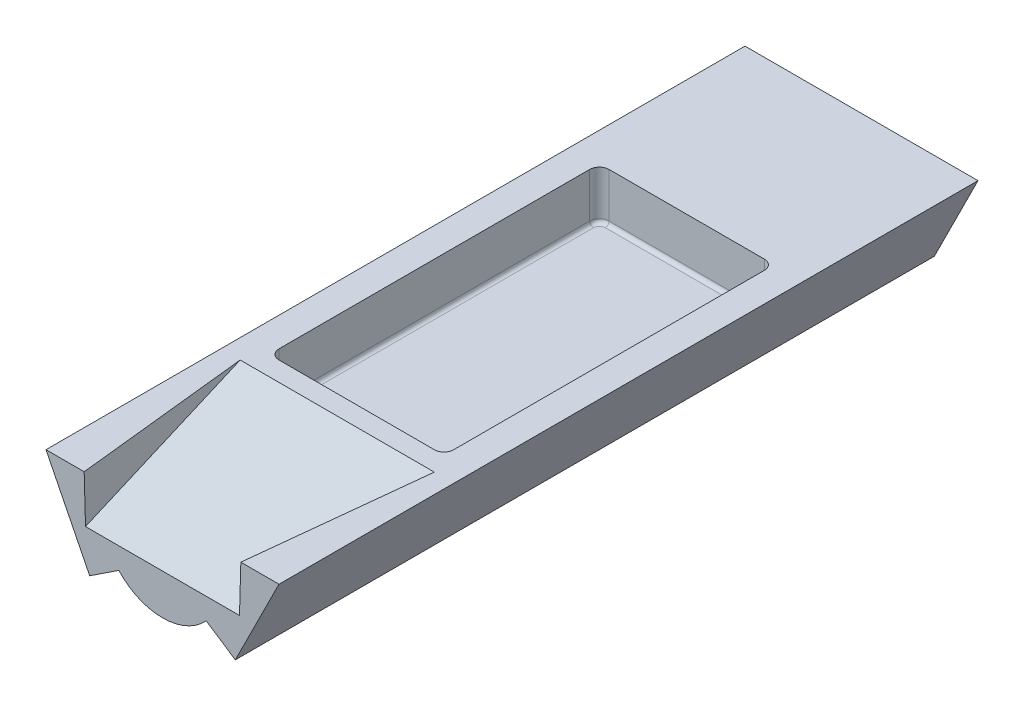
SolidWorks part; units mm, degrees
ref_plane "Front Plane" through (0, 0, 0) normal (0, 0, 1) x (1, 0, 0)
ref_plane "Top Plane" through (0, 0, 0) normal (0, 1, 0) x (1, 0, 0)
ref_plane "Right Plane" through (0, 0, 0) normal (1, 0, 0) x (0, 0, -1)
sketch "Sketch1" plane through (0, 0, 0) normal (0, 0, 1) x (1, 0, 0)
  line L6 (-304.8, 228.6) -> (304.8, 228.6)
  line L9 (0, 0) -> (0, 228.6) construction
  line L15 (-304.8, 228.6) -> (-190.5, 0)
  line L16 (-190.5, 0) -> (-114.3, 50.4)
  line L18 (190.5, 0) -> (304.8, 228.6)
  line L19 (190.5, 0) -> (114.3, 50.4)
  arc A0 (-114.3, 50.4) -> (114.3, 50.4) centre (0, 154.808) ccw
  dimension "D1" = 609.6
  dimension "D2" = 228.6
  dimension "D3" = 228.6
  dimension "D4" = 114.3
  dimension "D5" = 114.3
  dimension "D6" = 76.2
  dimension "D7" = 76.2
extrude "Boss-Extrude2" add sketch "Sketch1" against normal blind 1828.8
sketch "Sketch2" plane through (0, 228.6, 0) normal (0, 1, 0) x (1, 0, 0)
  line L1 (-203.2, 0) -> (203.2, 0)
  line L3 (-254, 457.2) -> (254, 457.2)
  line L6 (-254, 457.2) -> (-203.2, 0)
  line L7 (254, 457.2) -> (203.2, 0)
  line L8 (304.8, 0) -> (-304.8, 0) construction
  dimension "D1" = 508
  dimension "D2" = 457.2
  dimension "D3" = 50.8
  dimension "D4" = 50.8
ref_plane "Plane1" through (0, 98.9867, 26.5234) normal (0, 0.9659, 0.2588) x (1, 0, 0)
sketch "Sketch7" plane through (0, 98.9867, 26.5234) normal (0, 0.9659, 0.2588) x (1, 0, 0)
  line L1 (-254, 500.7873) -> (254, 500.7873)
  line L2 (-254, 500.7873) -> (-196.5534, -16.2318)
  line L3 (254, 500.7873) -> (196.5534, -16.2318)
  line L6 (-196.5534, -16.2318) -> (196.5534, -16.2318)
  point P2 (-190.5, -16.2318)
  point P3 (196.5534, -11.6943)
  dimension "D1" = 508
extrude "Cut-Extrude2" cut sketch "Sketch7" along normal through all
sketch "Sketch8" plane through (0, 228.6, 0) normal (0, 1, 0) x (1, 0, 0)
  line L0 (-304.8, 1828.8) -> (-304.8, 0) construction
  line L1 (-228.6, 508) -> (228.6, 508)
  line L2 (-228.6, 508) -> (-228.6, 1371.6)
  line L3 (-228.6, 1371.6) -> (228.6, 1371.6)
  line L4 (228.6, 508) -> (228.6, 1371.6)
  line L5 (254, 457.2) -> (-254, 457.2) construction
  dimension "D1" = 457.2
  dimension "D2" = 863.6
  dimension "D3" = 76.2
  dimension "D4" = 50.8
extrude "Cut-Extrude5" cut sketch "Sketch8" against normal blind 127
fillet "Fillet1" radius 10 4 edges at (0, 101.6, -1371.6) (228.6, 101.6, -939.8) (0, 101.6, -508) (-228.6, 101.6, -939.8)
fillet "Fillet2" radius 25.4 8 edges at (225.6711, 104.5289, -510.9289) (-225.6711, 104.5289, -510.9289) (-228.6, 170.1, -508) (228.6, 170.1, -508) (-225.6711, 104.5289, -1368.6711) (225.6711, 104.5289, -1368.6711) (228.6, 170.1, -1371.6) (-228.6, 170.1, -1371.6)
